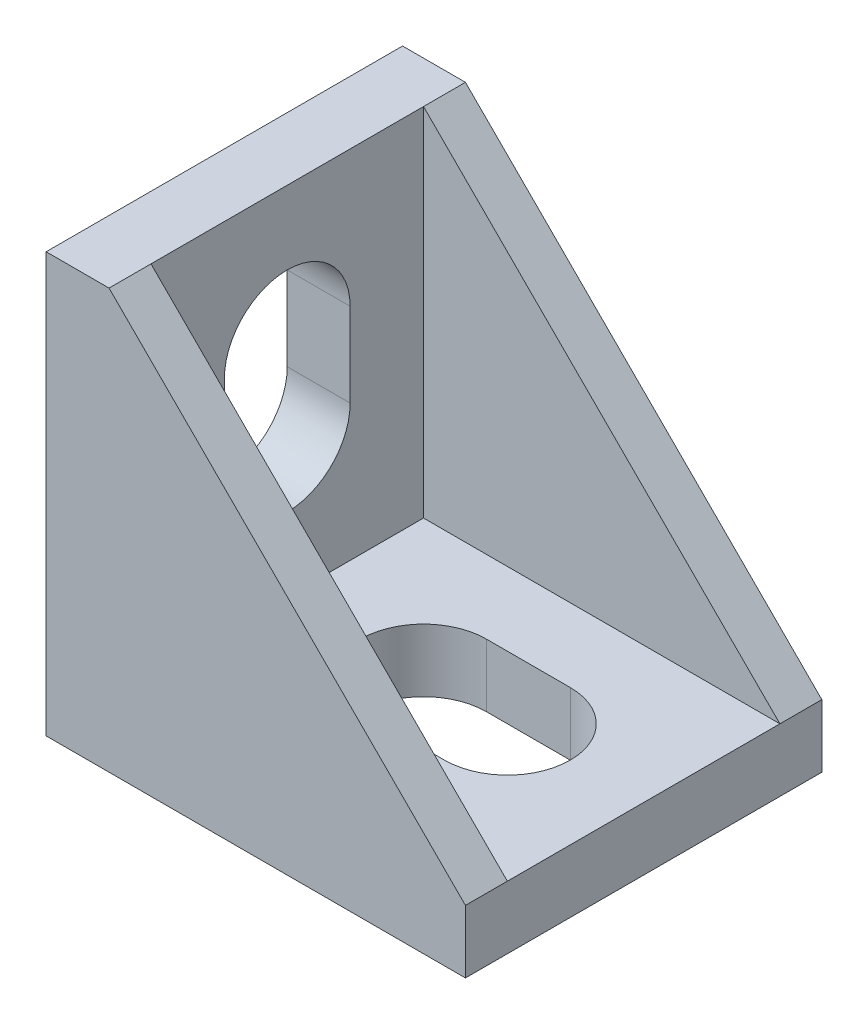
SolidWorks part; units mm, degrees
material "6061 Alloy"
ref_plane "Front Plane" through (0, 0, 0) normal (0, 0, 1) x (1, 0, 0)
ref_plane "Top Plane" through (0, 0, 0) normal (0, 1, 0) x (1, 0, 0)
ref_plane "Right Plane" through (0, 0, 0) normal (1, 0, 0) x (0, 0, -1)
sketch "Sketch1" plane through (0, 0, 0) normal (0, 0, 1) x (1, 0, 0)
  line L0 (0, 0) -> (0, 20)
  line L1 (0, 20) -> (3, 20)
  line L2 (3, 20) -> (3, 3)
  line L3 (3, 3) -> (20, 3)
  line L4 (20, 3) -> (20, 0)
  line L5 (20, 0) -> (0, 0)
  dimension "D1" = 20
  dimension "D2" = 20
  dimension "D3" = 3
extrude "Boss-Extrude1" add sketch "Sketch1" along normal blind 17
sketch "Sketch2" plane through (0, 0, 17) normal (0, 0, 1) x (1, 0, 0)
  line L0 (3, 20) -> (20, 3)
  line L1 (20, 3) -> (3, 3)
  line L2 (3, 3) -> (3, 20)
extrude "Boss-Extrude2" add sketch "Sketch2" against normal blind 2
sketch "Sketch3" plane through (0, 0, 0) normal (0, 0, -1) x (-1, 0, 0)
  line L0 (-3, 20) -> (-20, 3)
  line L1 (-20, 3) -> (-3, 3)
  line L2 (-3, 3) -> (-3, 20)
extrude "Boss-Extrude3" add sketch "Sketch3" against normal blind 2
hole_wizard "Ø6.0mm Dowel Slot1" positions "Sketch4" profile "Sketch5" size "Ø6.0" standard "ANSI Metric" slot yes end condition through all
sketch "Sketch4" plane through (0, 3, 0) normal (0, 1, 0) x (1, 0, 0)
  line L1 (6.5, -8.5) -> (16.5, -8.5) construction
  line L2 (20, -2) -> (3, -2) construction
  line L3 (11.5, -15) -> (11.5, -2) construction
  line L4 (3, -15) -> (20, -15) construction
  point P0 (11.5, -8.5)
  dimension "D1" = 10
sketch "Sketch5" plane through (11.5, 3, 8.5) normal (1, 0, 0) x (0, 0, 1)
  line L0 (0, 0) -> (0, 3)
  line L1 (0, 3) -> (3, 3)
  line L2 (3, 3) -> (3, 0)
  line L5 (3, 0) -> (0, 0)
  line L11 (0, -6.35) -> (0, 107.95) construction
  dimension "Thru Hole Dia." = 6
  dimension "Thru Hole Depth" = 3
hole_wizard "Ø6.0mm Dowel Slot2" positions "Sketch6" profile "Sketch7" size "Ø6.0" standard "ANSI Metric" slot yes end condition through all
sketch "Sketch6" plane through (3, 0, 0) normal (1, 0, 0) x (0, 0, -1)
  line L0 (-8.5, 16.5) -> (-8.5, 6.5) construction
  line L1 (-15, 20) -> (-15, 3) construction
  line L2 (-15, 11.5) -> (-2, 11.5) construction
  line L3 (-2, 3) -> (-2, 20) construction
  point P0 (-8.5, 11.5)
  dimension "D1" = 10
sketch "Sketch7" plane through (3, 11.5, 8.5) normal (0, 1, 0) x (0, 0, -1)
  line L0 (0, 0) -> (0, 3)
  line L1 (0, 3) -> (3, 3)
  line L2 (3, 3) -> (3, 0)
  line L5 (3, 0) -> (0, 0)
  line L11 (0, -6.35) -> (0, 107.95) construction
  dimension "Thru Hole Dia." = 6
  dimension "Thru Hole Depth" = 3
